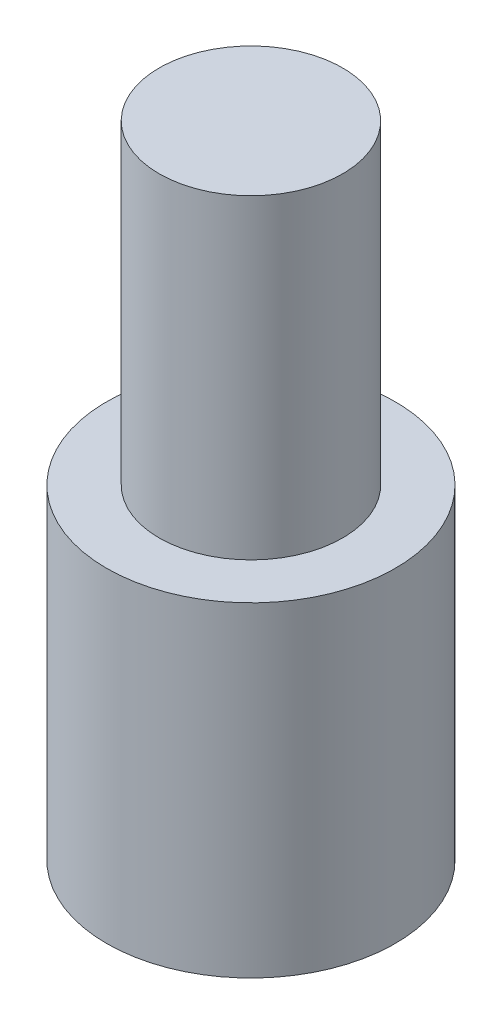
SolidWorks part; units mm, degrees
ref_plane "前视基准面" through (0, 0, 0) normal (0, 0, 1) x (1, 0, 0)
ref_plane "上视基准面" through (0, 0, 0) normal (0, 1, 0) x (1, 0, 0)
ref_plane "右视基准面" through (0, 0, 0) normal (1, 0, 0) x (0, 0, -1)
sketch "草图1" plane through (0, 0, 0) normal (0, 1, 0) x (1, 0, 0)
  circle A0 centre (-14.4643, 6.7518) radius 7.55
  dimension "D1" = 15.1
extrude "凸台-拉伸1" add sketch "草图1" along normal blind 17
sketch "草图2" plane through (0, 0, 0) normal (0, -1, 0) x (1, 0, 0)
  circle A0 centre (-14.4643, -6.7518) radius 5.15
  circle A1 centre (-14.4643, -6.7518) radius 7.55 construction
  dimension "D1" = 10.3
extrude "切除-拉伸1" cut sketch "草图2" against normal blind 2
sketch "草图3" plane through (0, 17, 0) normal (0, 1, 0) x (1, 0, 0)
  circle A0 centre (-14.4643, 6.7518) radius 4.8
  circle A1 centre (-14.4643, 6.7518) radius 7.55 construction
  dimension "D1" = 9.6
extrude "凸台-拉伸2" add sketch "草图3" along normal blind 16.5
